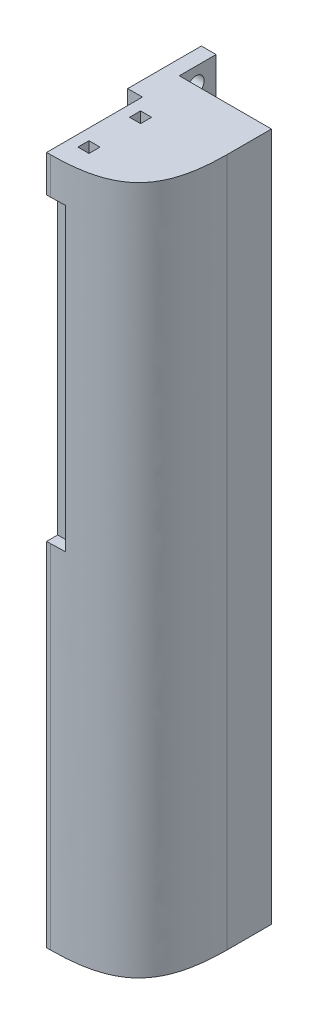
SolidWorks part; units mm, degrees
ref_plane "Front Plane" through (0, 0, 0) normal (0, 0, 1) x (1, 0, 0)
ref_plane "Top Plane" through (0, 0, 0) normal (0, 1, 0) x (1, 0, 0)
ref_plane "Right Plane" through (0, 0, 0) normal (1, 0, 0) x (0, 0, -1)
sketch "Sketch1" plane through (0, 0, 0) normal (0, 1, 0) x (1, 0, 0)
  line L1 (0, 0) -> (25, 0)
  line L2 (0, 0) -> (0, 36)
  line L3 (0, 36) -> (25, 36)
  line L4 (25, 0) -> (25, 36)
  dimension "D1" = 25
  dimension "D2" = 36
extrude "Boss-Extrude1" add sketch "Sketch1" along normal blind 186.9
fillet "Fillet1" radius 24 1 edges at (25, 93.45, 0) conic rho 0.55
ref_plane "Plane1" through (0, 0, 0) normal (0, 0, -1) x (-1, 0, 0)
sketch "Sketch2" plane through (0, 0, 0) normal (0, 0, -1) x (-1, 0, 0)
  line L1 (0, 176.9) -> (-5, 176.9)
  line L2 (0, 176.9) -> (0, 95.5)
  line L3 (0, 95.5) -> (-5, 95.5)
  line L4 (-5, 176.9) -> (-5, 95.5)
  line L5 (-1, 186.9) -> (-25, 186.9) construction
  dimension "D1" = 10
  dimension "D2" = 81.4
  dimension "D3" = 5
extrude "Cut-Extrude1" cut sketch "Sketch2" along normal blind 3
sketch "Sketch6" plane through (0, 0, -36) normal (0, 0, -1) x (-1, 0, 0)
  line L0 (0, 186.9) -> (0, 0) construction
  line L1 (0, 186.9) -> (4, 186.9)
  line L2 (0, 186.9) -> (0, 176.9)
  line L3 (0, 176.9) -> (4, 176.9)
  line L4 (4, 186.9) -> (4, 176.9)
  line L5 (0, 66.9) -> (4, 66.9)
  line L6 (0, 66.9) -> (0, 76.9)
  line L7 (0, 76.9) -> (4, 76.9)
  line L8 (4, 66.9) -> (4, 76.9)
  line L9 (-25, 186.9) -> (0, 186.9) construction
  dimension "D1" = 10
  dimension "D2" = 4
  dimension "D3" = 4
  dimension "D4" = 10
  dimension "D5" = 120
extrude "Boss-Extrude3" add sketch "Sketch6" against normal blind 10 and the other way blind 10
sketch "Sketch7" plane through (-4, 0, 0) normal (-1, 0, 0) x (0, 0, 1)
  line L0 (-36, 176.9) -> (-36, 76.9) construction
  line L1 (-46, 186.9) -> (-26, 186.9) construction
  line L2 (-46, 66.9) -> (-26, 66.9) construction
  line L3 (-36, 66.9) -> (-36, 0) construction
  circle A0 centre (-40.5, 182.4) radius 2.25
  circle A1 centre (-40.5, 71.4) radius 2.25
  dimension "D3" = 4.5
  dimension "D6" = 4.5
  dimension "D1" = 4.5
  dimension "D2" = 4.5
  dimension "D4" = 4.5
  dimension "D5" = 4.5
extrude "Cut-Extrude2" cut sketch "Sketch7" against normal up to next
chamfer "Chamfer1" distance 4 angle 45 1 edges at (0, 71.9, -26)
sketch "Sketch8" plane through (0, 0, 0) normal (-1, 0, 0) x (0, 0, 1)
  line L0 (-26, 186.9) -> (0, 186.9) construction
  line L1 (-10, 182.9) -> (-4, 182.9)
  line L2 (-10, 182.9) -> (-10, 178.9)
  line L3 (-10, 178.9) -> (-4, 178.9)
  line L4 (-4, 182.9) -> (-4, 178.9)
  line L5 (0, 13.75) -> (0, -13.75) construction
  line L7 (-24, 182.9) -> (-18, 182.9)
  line L8 (-24, 182.9) -> (-24, 178.9)
  line L9 (-24, 178.9) -> (-18, 178.9)
  line L10 (-18, 182.9) -> (-18, 178.9)
  dimension "D1" = 4
  dimension "D2" = 6
  dimension "D3" = 4
  dimension "D4" = 4
  dimension "D5" = 8
  dimension "D6" = 6
  dimension "D7" = 4
extrude "Cut-Extrude3" cut sketch "Sketch8" against normal blind 9
sketch "Sketch9" plane through (0, 186.9, 0) normal (0, 1, 0) x (1, 0, 0)
  line L0 (0, 0) -> (1, 0) construction
  line L1 (3, 5.5) -> (6, 5.5)
  line L2 (3, 5.5) -> (3, 8.5)
  line L3 (3, 8.5) -> (6, 8.5)
  line L4 (6, 5.5) -> (6, 8.5)
  line L5 (0, 26) -> (0, 0) construction
  line L7 (3, 19.5) -> (6, 19.5)
  line L8 (3, 19.5) -> (3, 22.5)
  line L9 (3, 22.5) -> (6, 22.5)
  line L10 (6, 19.5) -> (6, 22.5)
  dimension "D1" = 5.5
  dimension "D2" = 3
  dimension "D3" = 3
  dimension "D4" = 3
  dimension "D5" = 11
  dimension "D6" = 3
  dimension "D7" = 3
  dimension "D8" = 3
extrude "Cut-Extrude4" cut sketch "Sketch9" against normal blind 10
